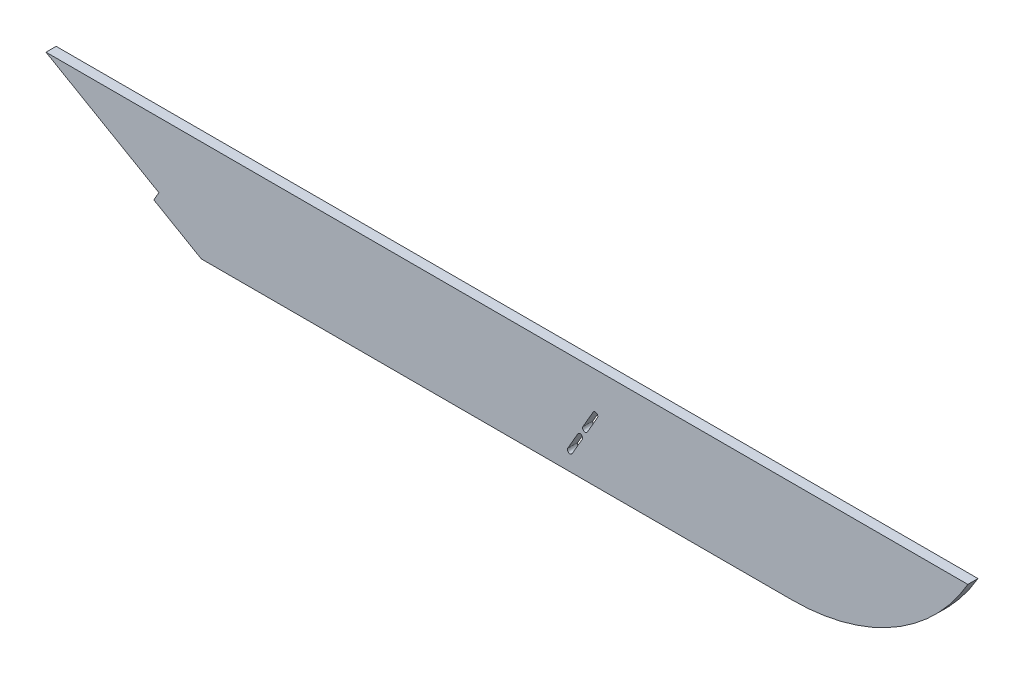
SolidWorks part; units mm, degrees
material "Plain Carbon Steel"
ref_plane "Front Plane" through (0, 0, 0) normal (0, 0, 1) x (1, 0, 0)
ref_plane "Top Plane" through (0, 0, 0) normal (0, 1, 0) x (1, 0, 0)
ref_plane "Right Plane" through (0, 0, 0) normal (1, 0, 0) x (0, 0, -1)
sketch "Sketch1" plane through (0, 0, 0) normal (0, 0, 1) x (1, 0, 0)
  line L0 (-3.75, -6.4952) -> (3.75, 6.4952) construction
  line L1 (-188.0475, -19.6891) -> (161.1325, -19.6891)
  line L3 (-264.61, 30.3109) -> (190, 30.3109)
  line L5 (-264.61, 30.3109) -> (-267.12, 25.9634)
  line L6 (-267.12, 25.9634) -> (-188.0475, -19.6891)
  line L7 (0, -55) -> (0, 55) construction
  line L8 (17.5, 30.3109) -> (-11.3675, -19.6891) construction
  line L9 (190, 30.3109) -> (161.1325, -19.6891)
  circle A0 centre (-3.75, -6.4952) radius 1.25
  circle A1 centre (3.75, 6.4952) radius 1.25
  point P1 (0, 0)
  point P8 (0, 0)
  dimension "D3" = 2.5
  dimension "D1" = 35
  dimension "D2" = 454.61
  dimension "D4" = 30
  dimension "D5" = 15
  dimension "D6" = 50
  dimension "D7" = 190
  dimension "D8" = 5.02
  dimension "D9" = 30
  dimension "D10" = 60
extrude "Boss-Extrude1" add sketch "Sketch1" along normal blind 5
sketch "Sketch2" plane through (0, 0, 0) normal (0, 0, 1) x (1, 0, 0)
  line L0 (6.25, 10.8253) -> (1.25, 2.1651) construction
  line L1 (7.3325, 10.2003) -> (2.3325, 1.5401)
  line L2 (5.1675, 11.4503) -> (0.1675, 2.7901)
  line L3 (-1.25, -2.1651) -> (-6.25, -10.8253) construction
  line L4 (-0.1675, -2.7901) -> (-5.1675, -11.4503)
  line L5 (-2.3325, -1.5401) -> (-7.3325, -10.2003)
  arc A0 (7.3325, 10.2003) -> (5.1675, 11.4503) centre (6.25, 10.8253) ccw
  arc A1 (0.1675, 2.7901) -> (2.3325, 1.5401) centre (1.25, 2.1651) ccw
  circle A2 centre (3.75, 6.4952) radius 1.25 construction
  arc A3 (-0.1675, -2.7901) -> (-2.3325, -1.5401) centre (-1.25, -2.1651) ccw
  arc A4 (-7.3325, -10.2003) -> (-5.1675, -11.4503) centre (-6.25, -10.8253) ccw
  circle A6 centre (-3.75, -6.4952) radius 1.25 construction
  point P2 (3.75, 6.4952)
  point P13 (-3.75, -6.4952)
  dimension "D1" = 10
extrude "Cut-Extrude1" cut sketch "Sketch2" along normal through all
fillet "Fillet1" radius 100 1 edges at (161.1325, -19.6891, 2.5)
sketch "Sketch3" plane through (0, 0, 0) normal (0, 0, 1) x (1, 0, 0)
  line L0 (-211.4432, -6.1816) -> (-267.12, 25.9634)
  line L1 (-211.4432, -6.1816) -> (-208.9432, -1.8514)
  line L2 (-267.12, 25.9634) -> (-264.62, 30.2936)
  line L3 (-208.9432, -1.8514) -> (-264.62, 30.2936)
  line L4 (-264.61, 30.3109) -> (-267.12, 25.9634) construction
  dimension "D1" = 5
  dimension "D2" = 64.29
extrude "Cut-Extrude2" cut sketch "Sketch3" along normal through all
